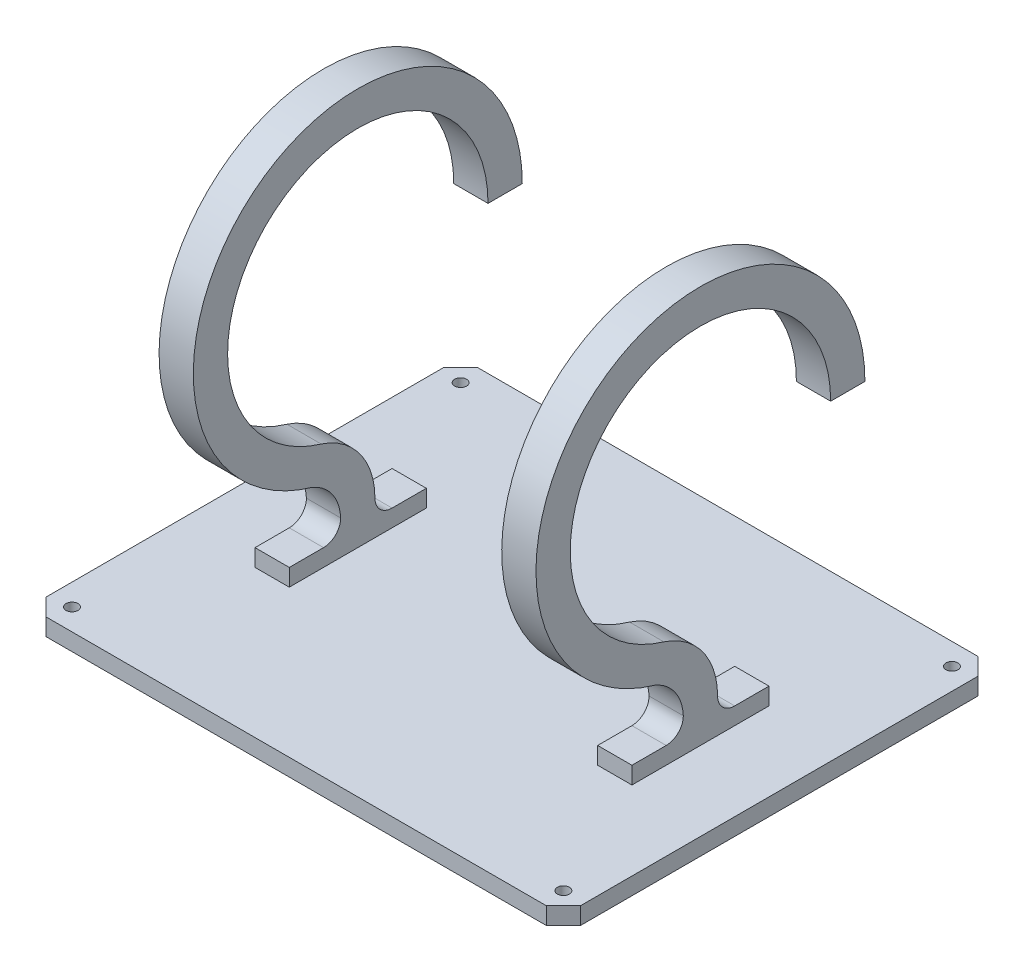
SolidWorks part; units mm, degrees
ref_plane "Front Plane" through (0, 0, 0) normal (0, 0, 1) x (1, 0, 0)
ref_plane "Top Plane" through (0, 0, 0) normal (0, 1, 0) x (1, 0, 0)
ref_plane "Right Plane" through (0, 0, 0) normal (1, 0, 0) x (0, 0, -1)
sketch "Sketch1" plane through (0, 0, 0) normal (0, 1, 0) x (1, 0, 0)
  line L1 (0, -26.2817) -> (156, -26.2817)
  line L2 (0, -26.2817) -> (0, 99.7183)
  line L3 (0, 99.7183) -> (156, 99.7183)
  line L4 (156, -26.2817) -> (156, 99.7183)
  dimension "D1" = 156
  dimension "D2" = 126
extrude "Boss-Extrude1" add sketch "Sketch1" along normal blind 5
chamfer "Chamfer1" distance 5 angle 45 4 edges at (156, 2.5, 26.2817) (156, 2.5, -99.7183) (0, 2.5, -99.7183) (0, 2.5, 26.2817)
sketch "Sketch2" plane through (0, 5, 0) normal (0, 1, 0) x (1, 0, 0)
  line L0 (5, 99.7183) -> (151, 99.7183) construction
  line L1 (5, 99.7183) -> (0, 99.7183)
  line L2 (5, 99.7183) -> (5, 94.7183)
  line L3 (5, 94.7183) -> (0, 94.7183)
  line L4 (0, 99.7183) -> (0, 94.7183)
  line L5 (0, 99.7183) -> (6.3, 99.7183)
  line L6 (0, 99.7183) -> (0, 93.4183)
  line L7 (0, 93.4183) -> (6.3, 93.4183)
  line L8 (6.3, 99.7183) -> (6.3, 93.4183)
  line L9 (151, 99.7183) -> (78, 99.7183) construction
  line L10 (78, 99.7183) -> (78, -26.2817) construction
  line L11 (78, -26.2817) -> (78, 36.7183) construction
  line L12 (78, 36.7183) -> (0, 36.7183) construction
  circle A0 centre (6.3, 93.4183) radius 1.75
  circle A1 centre (6.3, -19.9817) radius 1.75
  circle A2 centre (149.7, -19.9817) radius 1.75
  circle A3 centre (149.7, 93.4183) radius 1.75
  dimension "D3" = 3.5
  dimension "D1" = 6.3
  dimension "D2" = 6.3
extrude "Cut-Extrude1" cut sketch "Sketch2" against normal through all contours L7 A0 L8 | L8 A0 L7 | A2 | A3 | A1 region at (6.5476, 5, -93.1707) region at (5.5573, 5, -94.161) region at (149.7, 5, 19.9817) region at (149.7, 5, -93.4183)
sketch "Sketch3" plane through (0, 5, 0) normal (0, 1, 0) x (1, 0, 0)
  line L0 (0, 94.7183) -> (0, -21.2817) construction
  line L1 (0, -21.2817) -> (0, 36.7183) construction
  line L2 (0, 36.7183) -> (156, 36.7183) construction
  line L3 (156, 36.7183) -> (78, 36.7183) construction
  line L4 (78, 36.7183) -> (128, 36.7183) construction
  line L5 (128, 36.7183) -> (128, 99.7183) construction
  line L6 (123, 36.7183) -> (133, 36.7183)
  line L7 (128, 36.7183) -> (128, 56.7183)
  line L8 (123, 56.7183) -> (133, 56.7183)
  line L9 (133, 16.7183) -> (133, 56.7183)
  line L10 (123, 16.7183) -> (123, 56.7183)
  line L11 (123, 16.7183) -> (133, 16.7183)
  line L12 (78, 36.7183) -> (78, 99.7183) construction
  line L13 (33, 16.7183) -> (23, 16.7183)
  line L14 (23, 16.7183) -> (23, 56.7183)
  line L15 (33, 56.7183) -> (23, 56.7183)
  line L16 (33, 16.7183) -> (33, 56.7183)
  dimension "D1" = 50
  dimension "D2" = 5
  dimension "D3" = 40
  dimension "D4" = 20
extrude "Boss-Extrude2" add sketch "Sketch3" along normal blind 5 contours L6 L9 L8 L7 | L10 L6 L7 L8 | L10 L11 L9 L6 | L13 L14 L15 L16 region at (125.5, 5, -46.7183) region at (128, 5, -26.7183) region at (130.5, 5, -46.7183)
sketch "Sketch6" plane through (123, 0, 0) normal (-1, 0, 0) x (0, 0, 1)
  line L0 (-56.7183, 10) -> (-36.7183, 10) construction
  line L1 (-56.7183, 10) -> (-16.7183, 10)
  line L2 (-56.7183, 10) -> (-56.7183, 5)
  line L3 (-56.7183, 5) -> (-16.7183, 5)
  line L4 (-16.7183, 10) -> (-16.7183, 5)
  line L5 (-36.7183, 10) -> (-36.7183, 5) construction
  line L6 (-41.7183, 10) -> (-31.7183, 10)
  line L7 (-36.7183, 10) -> (-36.7183, 15)
  line L8 (-41.7183, 15) -> (-31.7183, 15)
  line L9 (-31.7183, 10) -> (-31.7183, 15)
  line L10 (-41.7183, 10) -> (-41.7183, 15)
  line L11 (-36.7183, 15) -> (-36.7183, 73) construction
  line L12 (-36.7183, 73) -> (-84.7183, 73) construction
  line L13 (-37.378, 28.3237) -> (-74.7183, 73) construction
  line L14 (-74.7183, 73) -> (-84.7183, 73)
  line L15 (-74.7183, 73) -> (-36.7183, 73)
  line L16 (-36.7183, 73) -> (1.2817, 73)
  line L17 (1.2817, 73) -> (11.2817, 73)
  line L18 (-26.0218, 36.5332) -> (-23.4793, 26.8619)
  line L19 (-26.0218, 36.5332) -> (-47.8816, 119.6838)
  arc A0 (-41.7183, 15) -> (-56.7183, 10) centre (-41.7183, -10) ccw
  arc A1 (-31.7183, 15) -> (-16.7183, 10) centre (-31.7183, -10) cw
  circle A2 centre (-36.7183, 73) radius 38
  arc A3 (-41.7183, 15) -> (-26.0218, 36.5332) centre (-19.1017, 15.0014) cw
  arc A4 (-31.7183, 15) -> (-23.4793, 26.8619) centre (-18.2259, 14.4207) cw
  circle A5 centre (-36.7183, 73) radius 48
  dimension "D3" = 96
  dimension "D4" = 76
  dimension "D5" = 58
  dimension "D6" = 10
  dimension "D1" = 5
  dimension "D2" = 5
  dimension "D7" = 58.226
extrude "Boss-Extrude3" add sketch "Sketch6" against normal blind 10 and the other way blind 100 contours L19 A5 L14 A2 | L17 A5 L19 A2 | L18 A5 L17 A2 L19 | A3 A5 L18 | A5 A3 L8 A4 | L1 L9 L8 L7 | L10 L6 L7 L8 region at (123, 12.5, -39.2183) region at (123, 20.4277, -35.1377) region at (123, 12.5, -34.2183) region at (123, 29.6005, -30.4283) region at (123, 48.8084, -4.5257) region at (123, 97.84, -68.1181) region at (123, 110.0837, -7.4568)
sketch "Sketch9" plane through (0, 5, 0) normal (0, 1, 0) x (1, 0, 0)
  line L1 (33, 56.7183) -> (123, 56.7183)
  line L2 (33, 56.7183) -> (33, 16.7183)
  line L3 (33, 16.7183) -> (123, 16.7183)
  line L4 (123, 56.7183) -> (123, 16.7183)
  line L5 (33, 84.7183) -> (123, 84.7183)
  line L6 (33, 84.7183) -> (33, -11.2817)
  line L7 (33, -11.2817) -> (123, -11.2817)
  line L8 (123, 84.7183) -> (123, -11.2817)
  line M18 (123, 16.7183) -> (123, 56.7183)
  line M21 (33, 56.7183) -> (33, 16.7183)
extrude "Cut-Extrude3" cut sketch "Sketch9" along normal through all contours L8 L5 L6 L1 | L3 L1 M21 M18 | L8 L3 L6 L7 region at (78, 5, -70.7183) region at (78, 5, -36.7183) region at (78, 5, -2.7183)
fillet "Fillet1" radius 5 4 edges at (28, 10, -41.7183) (28, 10, -31.7183) (128, 10, -31.7183) (128, 10, -41.7183)
